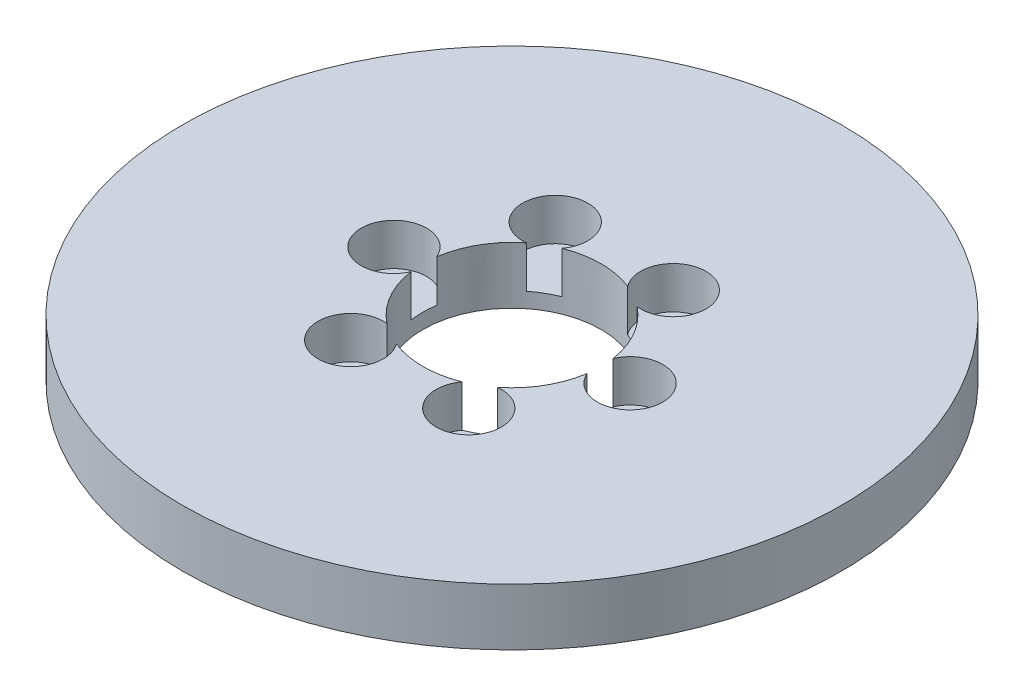
SolidWorks part; units mm, degrees
ref_plane "Front Plane" through (0, 0, 0) normal (0, 0, 1) x (1, 0, 0)
ref_plane "Top Plane" through (0, 0, 0) normal (0, 1, 0) x (1, 0, 0)
ref_plane "Right Plane" through (0, 0, 0) normal (1, 0, 0) x (0, 0, -1)
sketch "Sketch1" plane through (0, 0, 0) normal (0, 1, 0) x (1, 0, 0)
  circle A0 centre (0, 0) radius 92.5
  dimension "FLANGE_OD" = 185
extrude "Boss-Extrude1" add sketch "Sketch1" along normal blind 16
sketch "Sketch2" plane through (0, 0, 0) normal (0, 1, 0) x (1, 0, 0)
  circle A0 centre (0, 0) radius 25
  dimension "BORE_D" = 50
extrude "Cut-Extrude1" cut sketch "Sketch2" along normal through all
sketch "Sketch3" plane through (0, 16, 0) normal (0, 1, 0) x (1, 0, 0)
  circle A0 centre (0, 0) radius 33.1452 construction
  circle A1 centre (-33.1452, 0) radius 9.1646
  dimension "BOLT_D" = 18.3292
  dimension "BOLT_PCD" = 66.2905
extrude "Cut-Extrude2" cut sketch "Sketch3" against normal blind 11.7636
pattern_circular "CirPattern1" count 6 over 360 about axis through (0, 0, 0) along (0, 1, 0) of "Cut-Extrude2"
